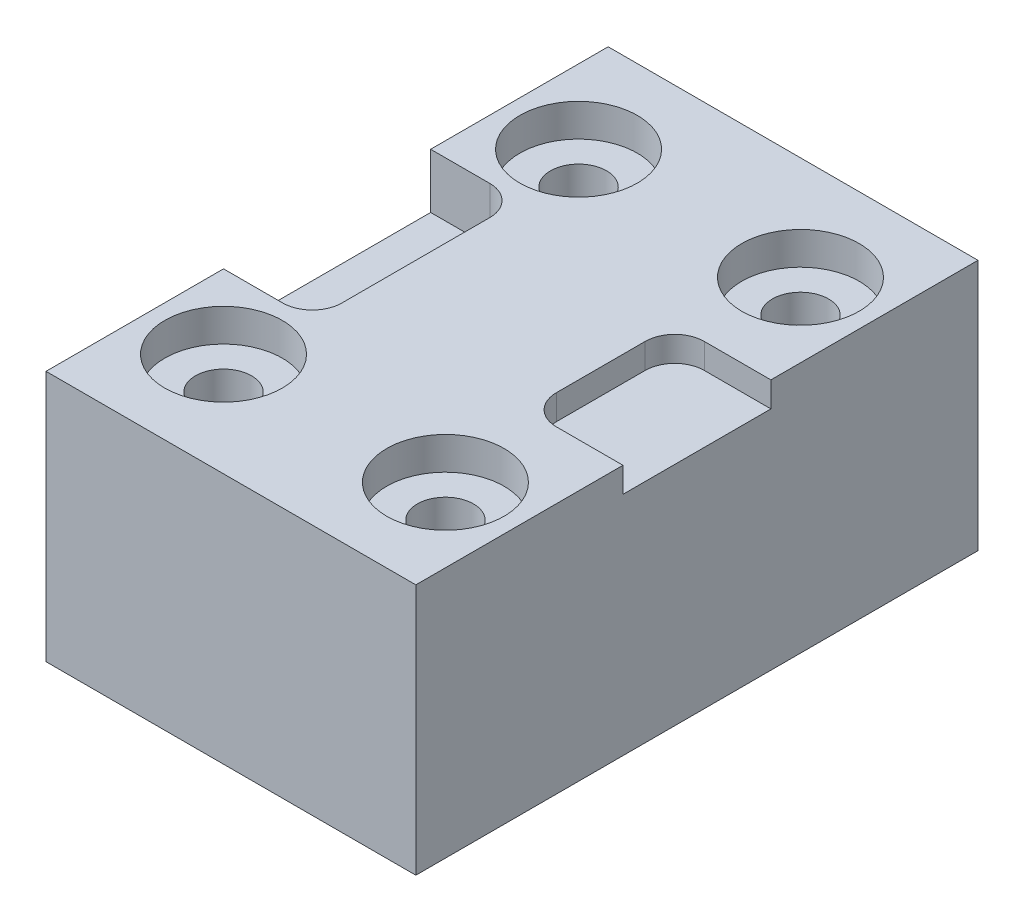
SolidWorks part; units mm, degrees
material "6063-T5"
ref_plane "Front Plane" through (0, 0, 0) normal (0, 0, 1) x (1, 0, 0)
ref_plane "Top Plane" through (0, 0, 0) normal (0, 1, 0) x (1, 0, 0)
ref_plane "Right Plane" through (0, 0, 0) normal (1, 0, 0) x (0, 0, -1)
sketch "Sketch1" plane through (0, 0, 0) normal (0, 1, 0) x (1, 0, 0)
  line L1 (-18493.9467, 11317.1913) -> (-18468.9467, 11317.1913)
  line L2 (-18493.9467, 11317.1913) -> (-18493.9467, 11279.1913)
  line L3 (-18493.9467, 11279.1913) -> (-18468.9467, 11279.1913)
  line L4 (-18468.9467, 11317.1913) -> (-18468.9467, 11279.1913)
  dimension "D1" = 25
  dimension "D2" = 38
extrude "Boss-Extrude1" add sketch "Sketch1" along normal blind 17
sketch "Sketch2" plane through (0, 17, 0) normal (0, 1, 0) x (1, 0, 0)
  line L0 (-18493.9467, 11298.1913) -> (-18468.9467, 11298.1913)
  line L1 (-18493.9467, 11317.1913) -> (-18493.9467, 11279.1913) construction
  line L2 (-18468.9467, 11279.1913) -> (-18468.9467, 11317.1913) construction
  line L3 (-18491.9467, 11305.1913) -> (-18493.9467, 11305.1913)
  line L4 (-18489.9467, 11291.1913) -> (-18491.9467, 11291.1913)
  line L5 (-18487.9467, 11293.1913) -> (-18487.9467, 11303.1913)
  line L6 (-18489.9467, 11305.1913) -> (-18491.9467, 11305.1913)
  line L7 (-18493.9467, 11300.1913) -> (-18493.9467, 11314.1913)
  line L8 (-18487.9467, 11291.1913) -> (-18493.9467, 11305.1913) construction
  line L9 (-18487.9467, 11305.1913) -> (-18493.9467, 11291.1913) construction
  line L10 (-18470.9467, 11293.1913) -> (-18473.4467, 11293.1913)
  line L11 (-18468.9467, 11293.1913) -> (-18468.9467, 11303.1913)
  line L12 (-18470.9467, 11303.1913) -> (-18473.4467, 11303.1913)
  line L13 (-18475.4467, 11295.1913) -> (-18475.4467, 11301.1913)
  line L14 (-18468.9467, 11293.1913) -> (-18475.4467, 11303.1913) construction
  line L15 (-18468.9467, 11303.1913) -> (-18475.4467, 11293.1913) construction
  line L16 (-18491.9467, 11291.1913) -> (-18493.9467, 11291.1913)
  line L17 (-18470.9467, 11303.1913) -> (-18468.9467, 11303.1913)
  line L18 (-18470.9467, 11293.1913) -> (-18468.9467, 11293.1913)
  line L19 (-18488.9467, 11286.1913) -> (-18488.9467, 11310.1913)
  line L20 (-18488.9467, 11286.1913) -> (-18473.9467, 11286.1913)
  line L21 (-18488.9467, 11310.1913) -> (-18473.9467, 11310.1913)
  line L22 (-18473.9467, 11286.1913) -> (-18473.9467, 11310.1913)
  line L23 (-18488.9467, 11286.1913) -> (-18473.9467, 11310.1913) construction
  line L24 (-18488.9467, 11310.1913) -> (-18473.9467, 11286.1913) construction
  arc A0 (-18489.9467, 11291.1913) -> (-18487.9467, 11293.1913) centre (-18489.9467, 11293.1913) ccw
  arc A1 (-18487.9467, 11303.1913) -> (-18489.9467, 11305.1913) centre (-18489.9467, 11303.1913) ccw
  arc A5 (-18473.4467, 11303.1913) -> (-18475.4467, 11301.1913) centre (-18473.4467, 11301.1913) ccw
  arc A6 (-18473.4467, 11293.1913) -> (-18475.4467, 11295.1913) centre (-18473.4467, 11295.1913) cw
  point P6 (-18490.9467, 11298.1913)
  point P11 (-18472.1967, 11298.1913)
  point P16 (-18492.9467, 11291.1913)
  point P25 (-18481.4467, 11298.1913)
  line M12 (-18493.9467, 11317.1913) -> (-18493.9467, 11279.1913)
  dimension "D7" = 2
  dimension "D8" = 5
  dimension "D9" = 5
  dimension "D10" = 5
  dimension "D1" = 12.5
  dimension "D2" = 0
  dimension "D3" = 6
  dimension "D4" = 0
  dimension "D5" = 10
  dimension "D6" = 14
  dimension "D11" = 5
extrude "Cut-Extrude3" cut sketch "Sketch2" against normal offset from surface (3.7 mm away) 13.3 contours L5 A1 L6 L3 L0 M12 | L4 A0 L5 L0 L16 M12 | L5 A1 L19 L0 | L19 A0 L5 L0 region at (-18491.4523, 17, -11301.6828) region at (-18491.4523, 17, -11294.6998) region at (-18488.4645, 17, -11301.3181) region at (-18488.4645, 17, -11295.0644) up to face at (-18481.4467, 0, -11298.1913)
extrude "Cut-Extrude4" cut sketch "Sketch2<6>" against normal offset from surface (1.7 mm away) 15.3 contours L12 A5 L13 L0 L11 | A6 L10 L11 L0 L13 | L22 A5 L13 L0 | A6 L22 L0 L13 region at (-18474.6562, 17, -11300.4302) region at (-18474.6562, 17, -11295.9523) region at (-18471.4457, 17, -11300.6902) region at (-18471.4457, 17, -11295.6923) up to face at (-18481.4467, 0, -11298.1913)
sketch "Sketch2<6>" plane through (0, 17, 0) normal (0, 1, 0) x (1, 0, 0) same geometry as "Sketch2"
hole_wizard "CBORE for #6 Binding Head Machine Screw1" positions "Sketch10" profile "Sketch11" counterbore size "#6" standard "ANSI Inch" end condition through all
sketch "Sketch10" plane through (0, 17, 0) normal (0, 1, 0) x (1, 0, 0)
  point P0 (-18488.9467, 11310.1913)
  point P3 (-18473.9467, 11310.1913)
  point P6 (-18473.9467, 11286.1913)
  point P9 (-18488.9467, 11286.1913)
sketch "Sketch11" plane through (-18488.9467, 17, -11310.1913) normal (1, 0, 0) x (0, 0, 1)
  line L0 (0, 0) -> (0, 17)
  line L1 (0, 17) -> (1.8986, 17)
  line L3 (1.8986, 17) -> (1.8986, 2.2098)
  line L4 (1.8986, 2.2098) -> (3.9687, 2.2098)
  line L5 (3.9687, 2.2098) -> (3.9687, 0)
  line L7 (3.9687, 0) -> (0, 0)
  line L11 (0, -6.35) -> (0, 107.95) construction
  dimension "Thru Hole Dia." = 3.7973
  dimension "Thru Hole Depth" = 17
  dimension "C'Bore Dia." = 7.9375
  dimension "C'Bore Depth" = 2.2098
